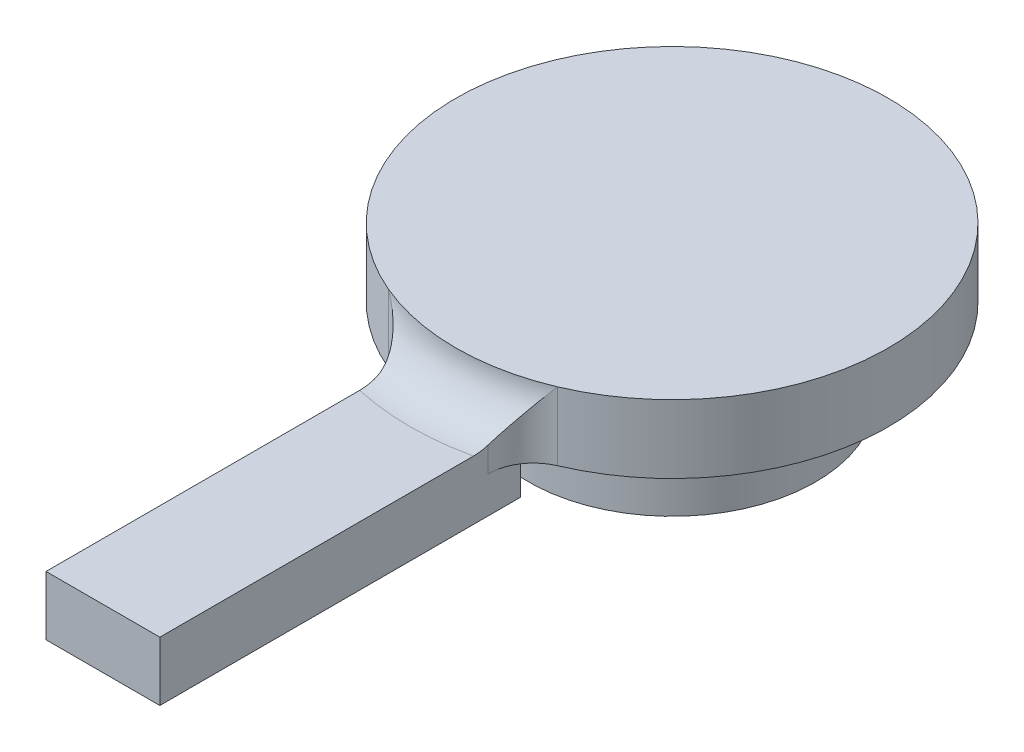
SolidWorks part; units mm, degrees
ref_plane "前视基准面" through (0, 0, 0) normal (0, 0, 1) x (1, 0, 0)
ref_plane "上视基准面" through (0, 0, 0) normal (0, 1, 0) x (1, 0, 0)
ref_plane "右视基准面" through (0, 0, 0) normal (1, 0, 0) x (0, 0, -1)
other "Configuration Table"
sketch "草图1" plane through (0, 0, 0) normal (0, 1, 0) x (1, 0, 0)
  circle A0 centre (0, 0) radius 9.5
  dimension "D1" = 19
extrude "凸台-拉伸1" add sketch "草图1" along normal blind 3 contours A0
sketch "草图2" plane through (0, 0, 0) normal (0, -1, 0) x (-1, 0, 0)
  circle A0 centre (0, 0) radius 7.6
  dimension "D1" = 15.2
extrude "切除-拉伸1" cut sketch "草图2" against normal blind 0.5
sketch "草图3" plane through (0, 0, 0) normal (0, -1, 0) x (1, 0, 0)
  line L1 (-2.5, 0) -> (2.5, 0)
  line L2 (-2.5, 0) -> (-2.5, 25)
  line L3 (-2.5, 25) -> (2.5, 25)
  line L4 (2.5, 0) -> (2.5, 25)
  circle A0 centre (0, 0) radius 9.5
  circle A2 centre (0, 0) radius 9.5 construction
  circle M5 centre (0, 0) radius 9.5
  dimension "D1" = 5
  dimension "D2" = 25
extrude "凸台-拉伸2" add sketch "草图3" along normal blind 2.6 from offset 1 contours L4 L3 L2 M5 region at (0, 0, 17.1943) offset against normal yes
sketch "草图4" plane through (0, 0.5, 0) normal (0, -1, 0) x (1, 0, 0)
  circle A0 centre (0, 0) radius 6.3
  dimension "D1" = 12.6
extrude "凸台-拉伸3" add sketch "草图4" along normal blind 4.2
sketch "草图5" plane through (0, -3.7, 0) normal (0, -1, 0) x (1, 0, 0)
  circle A0 centre (0, 0) radius 1
  dimension "D1" = 2
extrude "切除-拉伸2" cut sketch "草图5" against normal blind 5
sketch "草图6" plane through (0, -1.6, 0) normal (0, -1, 0) x (-1, 0, 0)
  line L0 (2.5, -17.0826) -> (-2.5, -17.0826) construction
  line L1 (2.5, -9.1652) -> (2.5, -25) construction
  line L2 (-2.5, -9.1652) -> (-2.5, -25) construction
  circle A0 centre (0, -17.0826) radius 0.6
  dimension "D1" = 1.2
extrude "切除-拉伸3" cut sketch "草图6" against normal blind 2.4
fillet "圆角1" radius 2 1 edges at (0, 1, 9.5)
fillet "圆角2" radius 2 2 edges at (2.5, 1.5, 9.1652) (-2.5, 1.5, 9.1652)
